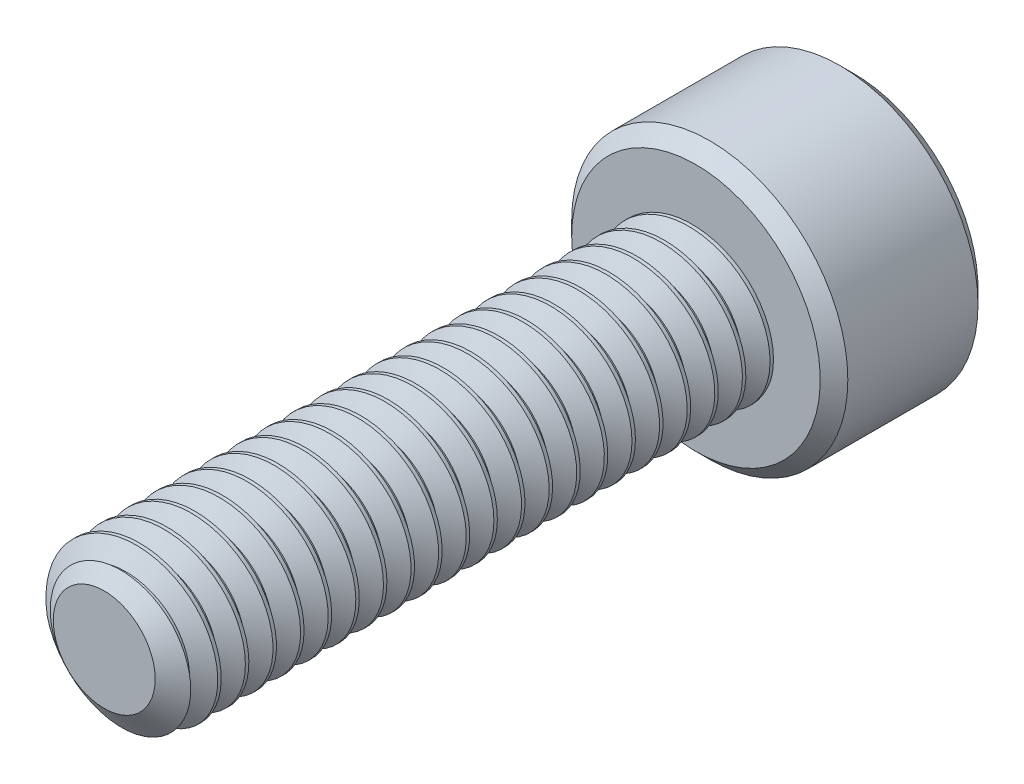
SolidWorks part; units mm, degrees
ref_plane "Front Plane" through (0, 0, 0) normal (0, 0, 1) x (1, 0, 0)
ref_plane "Top Plane" through (0, 0, 0) normal (0, 1, 0) x (1, 0, 0)
ref_plane "Right Plane" through (0, 0, 0) normal (1, 0, 0) x (0, 0, -1)
sketch "Sketch1" plane through (0, 0, 0) normal (0, 0, 1) x (1, 0, 0)
  circle A0 centre (0, 0) radius 2
  dimension "OD" = 4
extrude "Extrude1" add sketch "Sketch1" against normal blind 15
sketch "Sketch2" plane through (0, 0, 0) normal (0, 0, 1) x (1, 0, 0)
  circle A0 centre (0, 0) radius 2 construction
  circle A1 centre (0, 0) radius 2
curve "Helix/Spiral1" pitch 0.7 height 15.7 radius 2 centre (0, 0, 0) axis (0, 0, -1) start towards (0, 1, 0) parameters "pitch"=0.7
sketch "Sketch3" plane through (0, 0, 0) normal (1, 0, 0) x (0, 0, -1)
  line L0 (-0.6125, 2) -> (-0.35, 1.5453)
  line L1 (-0.35, 1.5453) -> (-0.2625, 1.5453)
  line L2 (-0.2625, 1.5453) -> (0, 2)
  line L3 (-0.6125, 2) -> (0, 2)
  line L4 (-0.3062, 2) -> (-0.3062, 1.5453) construction
  line L5 (-0.4812, 1.7727) -> (-0.1312, 1.7727) construction
  line L6 (0, 2) -> (0, -2) construction
  dimension "D1" = 0.0875
  dimension "D2" = 0.35
  dimension "D3" = 60
sweep "Cut-Sweep1" cut profiles "Sketch3" path "Helix/Spiral1"
sketch "Sketch4" plane through (0, 0, 0) normal (1, 0, 0) x (0, 0, -1)
  line L0 (0.4962, 2) -> (0, 1.2913)
  line L1 (0, 1.2913) -> (0, 2)
  line L2 (0.4962, 2) -> (0, 2)
  line L3 (-0.6125, 2) -> (0, 2) construction
  line L4 (0, 0) -> (7.0209, 0) construction
  dimension "D1" = 55
  dimension "D2" = 0.254
revolve "Cut-Revolve1" cut sketch "Sketch4" angle 360 about L4
sketch "Sketch5" plane through (0, 0, 0) normal (1, 0, 0) x (0, 0, -1)
  line L0 (15, -0.6429) -> (15, 1.6418) construction
  line L1 (15, 2.127) -> (24.2679, 2.127)
  line L2 (15, 2.127) -> (15, 0)
  line L3 (15, 0) -> (24, 0)
  line L4 (24, 1.127) -> (24, 0)
  line L5 (24.2679, 2.127) -> (24, 1.127)
  line L6 (0, 0) -> (24, 0) construction
  point P3 (24, 2.127)
  point P10 (24, 2.127)
  dimension "D1" = 1
  dimension "D2" = 0.127
  dimension "D3" = 15
  dimension "Thread Min" = 24
revolve "partially thread" [suppressed] add sketch "Sketch5" angle 360 about L6
sketch "Sketch6" plane through (0, 0, -15) normal (0, 0, -1) x (-1, 0, 0)
  circle A0 centre (0, 0) radius 3.5
  dimension "head dia" = 7
extrude "Extrude2" add sketch "Sketch6" along normal blind 4
sketch "Sketch7" plane through (0, 0, -19) normal (0, 0, -1) x (-1, 0, 0)
  line L1 (0, 1.7321) -> (-1.5, 0.866)
  line L2 (-1.5, 0.866) -> (-1.5, -0.866)
  line L3 (-1.5, -0.866) -> (0, -1.7321)
  line L4 (0, -1.7321) -> (1.5, -0.866)
  line L5 (1.5, -0.866) -> (1.5, 0.866)
  line L6 (1.5, 0.866) -> (0, 1.7321)
  circle A0 centre (0, 0) radius 1.5 construction
  dimension "hex dia" = 3
extrude "Cut-Extrude1" cut sketch "Sketch7" against normal blind 2.25
sketch "Sketch8" plane through (0, 0, -19) normal (0, 0, -1) x (-1, 0, 0)
  circle A0 centre (0, 0) radius 1.7321
extrude "Cut-Extrude2" cut sketch "Sketch8" against normal through all draft 45
chamfer "Chamfer1" distance 0.35 angle 45 2 edges at (-3.5, 0, -19) (-3.5, 0, -15)
sketch "Sketch9" plane through (0, 0, 0) normal (1, 0, 0) x (0, 0, -1)
  line L0 (0, 2) -> (0, -2) construction
  line L1 (3.85, 2) -> (3.85, -2) construction
  dimension "D1" = 3.85
equation "\"D3@Helix/Spiral1\" = \"screw length@Extrude1\"+\"pitch@Helix/Spiral1\""
equation "\"D1@Sketch3\" = \"pitch@Helix/Spiral1\"*.125"
equation "\"D2@Sketch3\" = \"pitch@Helix/Spiral1\"*.5"
equation "\"D1@Cut-Extrude1\" = \"hex dia@Sketch7\"*.75"
equation "\"D1@Chamfer1\" = \"head dia@Sketch6\"*.05"
equation "\"D1@Sketch9\" = \"pitch@Helix/Spiral1\"*5.5"
